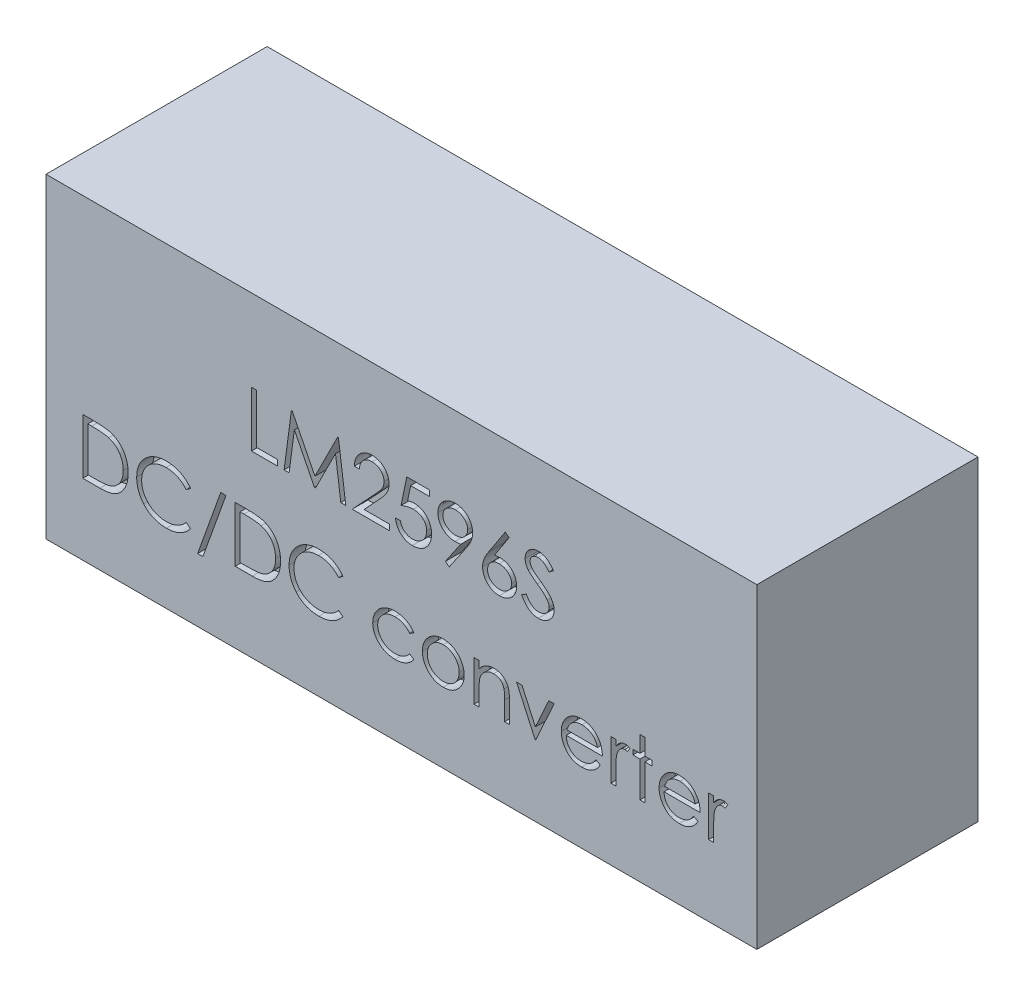
SolidWorks part; units mm, degrees
ref_plane "정면" through (0, 0, 0) normal (0, 0, 1) x (1, 0, 0)
ref_plane "윗면" through (0, 0, 0) normal (0, 1, 0) x (1, 0, 0)
ref_plane "우측면" through (0, 0, 0) normal (1, 0, 0) x (0, 0, -1)
sketch "스케치2" plane through (0, 0, 0) normal (0, 0, 1) x (1, 0, 0)
  line L1 (-22.5, 10) -> (22.5, 10)
  line L2 (-22.5, 10) -> (-22.5, -10)
  line L3 (-22.5, -10) -> (22.5, -10)
  line L4 (22.5, 10) -> (22.5, -10)
  line L5 (-22.5, 10) -> (22.5, -10) construction
  line L6 (-22.5, -10) -> (22.5, 10) construction
  point P0 (0, 0)
  dimension "D1" = 20
  dimension "4.5" = 45
extrude "보스-돌출1" add sketch "스케치2" along normal blind 14
sketch "스케치3" plane through (0, 0, 14) normal (0, 0, 1) x (1, 0, 0)
  line L0 (-22.5, 1.3292) -> (22.5, 1.3292) construction
  line L1 (-22.5, 10) -> (-22.5, -10) construction
  line L2 (22.5, -10) -> (22.5, 10) construction
  text T0 "LM2596S\r\nDC/DC converter"
extrude "컷-돌출1" cut sketch "스케치3" against normal blind 1
